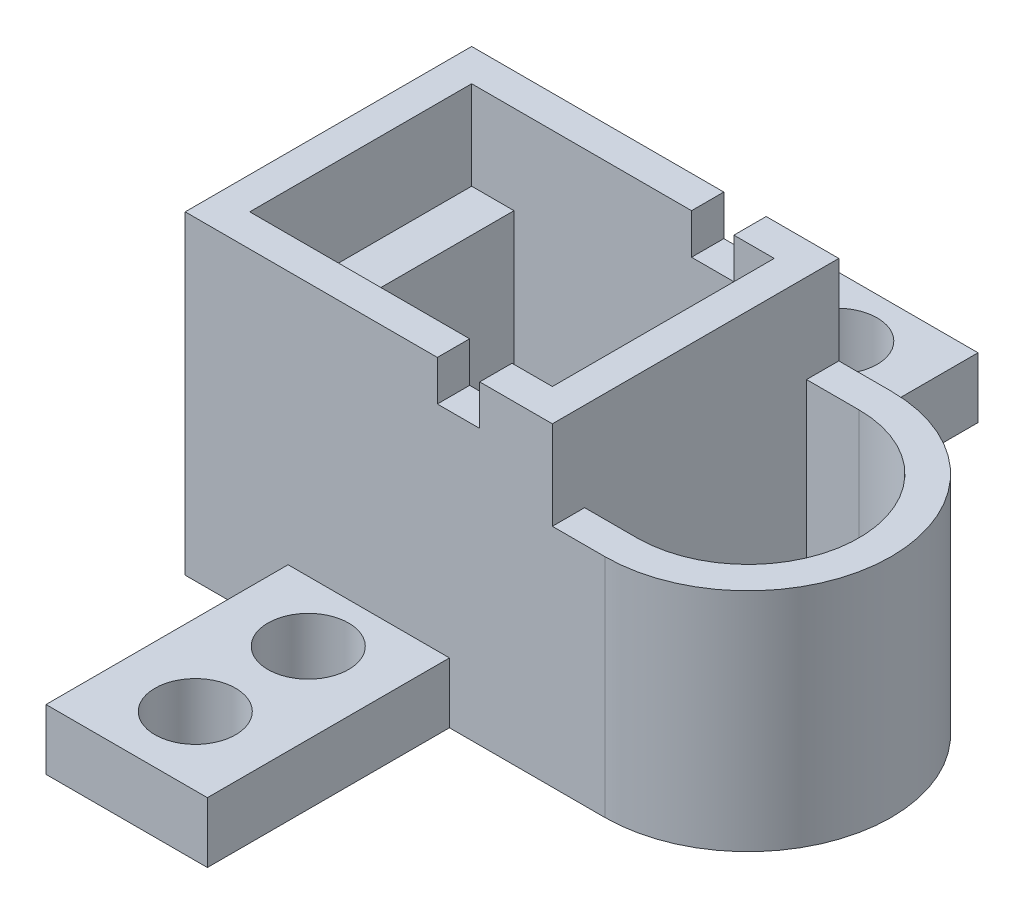
SolidWorks part; units mm, degrees
ref_plane "Спереди" through (0, 0, 0) normal (0, 0, 1) x (1, 0, 0)
ref_plane "Сверху" through (0, 0, 0) normal (0, 1, 0) x (1, 0, 0)
ref_plane "Справа" through (0, 0, 0) normal (1, 0, 0) x (0, 0, -1)
sketch "Эскиз1" plane through (0, 0, 0) normal (0, 1, 0) x (1, 0, 0)
  line L0 (4.55, 2.75) -> (5.85, 2.75)
  line L1 (-3.75, -2.75) -> (3.75, -2.75)
  line L2 (-3.75, -2.75) -> (-3.75, 2.75)
  line L3 (-3.75, 2.75) -> (3.75, 2.75)
  line L4 (3.75, -2.75) -> (3.75, 2.75)
  line L5 (-3.75, -2.75) -> (3.75, 2.75) construction
  line L6 (-3.75, 2.75) -> (3.75, -2.75) construction
  line L7 (-4.55, -3.55) -> (4.55, -3.55)
  line L8 (-4.55, -3.55) -> (-4.55, 3.55)
  line L9 (-4.55, 3.55) -> (4.55, 3.55)
  line L10 (4.55, -3.55) -> (4.55, 3.55)
  line L11 (-4.55, -3.55) -> (4.55, 3.55) construction
  line L12 (-4.55, 3.55) -> (4.55, -3.55) construction
  line L13 (-2.7, -2.75) -> (2.7, -2.75)
  line L14 (-2.7, -2.75) -> (-2.7, 2.75)
  line L15 (-2.7, 2.75) -> (2.7, 2.75)
  line L16 (2.7, -2.75) -> (2.7, 2.75)
  line L17 (-2.7, -2.75) -> (2.7, 2.75) construction
  line L18 (-2.7, 2.75) -> (2.7, -2.75) construction
  line L19 (4.55, -2.75) -> (5.85, -2.75)
  line L20 (4.55, 3.55) -> (5.85, 3.55)
  line L21 (4.55, -3.55) -> (5.85, -3.55)
  line L22 (5.85, 2.75) -> (5.85, -2.75) construction
  arc A0 (5.85, -2.75) -> (5.85, 2.75) centre (5.85, 0) ccw
  arc A1 (5.85, 3.55) -> (5.85, -3.55) centre (5.85, 0) cw
  point P0 (0, 0)
  point P6 (0, 0)
  point P10 (6.3693, 3.55)
  point P11 (0, 0)
  point P17 (0, 0)
  point P25 (0, 0)
  point P26 (7.3906, 3.55)
  dimension "D6" = 1.3
  dimension "D7" = 3.55
  dimension "D10" = 2.75
  dimension "D1" = 5.5
  dimension "D2" = 7.5
  dimension "D3" = 0.8
  dimension "D4" = 0.8
  dimension "D5" = 5.4
  dimension "D8" = 0.8
  dimension "D9" = 0.8
extrude "Бобышка-Вытянуть1" add sketch "Эскиз1" along normal blind 7.2 contours L7 L10 L9 L8 L4 L1 L2 L3 region at (4.4346, 0, 0)
extrude "Бобышка-Вытянуть2" add sketch "Эскиз1<3>" along normal blind 5 contours L1 L14 L3 L2 | L16 L1 L4 L3 region at (-3.225, 0, 0) region at (3.225, 0, 0)
sketch "Эскиз1<3>" plane through (0, 0, 0) normal (0, 1, 0) x (1, 0, 0) same geometry as "Эскиз1"
extrude "Бобышка-Вытянуть3" add sketch "Эскиз1<4>" against normal blind 0.6 contours L8 L9 L10 L7
sketch "Эскиз1<4>" plane through (0, 0, 0) normal (0, 1, 0) x (1, 0, 0) same geometry as "Эскиз1"
extrude "Бобышка-Вытянуть4" add sketch "Эскиз1<5>" along normal blind 5 contours A1 L20 L10 L0 A0 L19 L21 region at (4.636, 0, -3.15)
sketch "Эскиз1<5>" plane through (0, 0, 0) normal (0, 1, 0) x (1, 0, 0) same geometry as "Эскиз1"
extrude "Бобышка-Вытянуть5" add sketch "Эскиз1<6>" against normal blind 0.6 contours L19 A0 L0 L10 | A1 L20 L10 L0 A0 L19 L21 region at (4.636, 0, -3.15) region at (6.3344, 0, 0)
sketch "Эскиз1<6>" plane through (0, 0, 0) normal (0, 1, 0) x (1, 0, 0) same geometry as "Эскиз1"
sketch "Эскиз2" plane through (0, 0, -3.55) normal (0, 0, -1) x (-1, 0, 0)
  line L0 (4.55, 7.2) -> (-4.55, 7.2) construction
  line L1 (-1.7, 6.2) -> (-2.75, 6.2)
  line L2 (-1.7, 6.2) -> (-1.7, 7.2)
  line L3 (-1.7, 7.2) -> (-2.75, 7.2)
  line L4 (-2.75, 6.2) -> (-2.75, 7.2)
  line L5 (-1.7, 6.2) -> (-2.75, 7.2) construction
  line L6 (-1.7, 7.2) -> (-2.75, 6.2) construction
  line L7 (-4.55, 7.2) -> (-4.55, 5) construction
  point P0 (-2.225, 6.7)
  dimension "D1" = 1.05
  dimension "D2" = 1
  dimension "D3" = 1.8
extrude "Вырез-Вытянуть1" cut sketch "Эскиз2" against normal blind 7.1
sketch "Эскиз4" plane through (0, 0, 3.55) normal (0, 0, 1) x (1, 0, 0)
  line L0 (-2, -0.6) -> (2, -0.6)
  line L1 (-2, -0.6) -> (-2, 0.9)
  line L2 (2, -0.6) -> (2, 0.9)
  line L3 (-2, 0.9) -> (2, 0.9)
  line L4 (-4.55, -0.6) -> (5.85, -0.6) construction
  dimension "D1" = 4
  dimension "D2" = 1.5
extrude "Бобышка-Вытянуть7" add sketch "Эскиз4" along normal blind 6
sketch "Эскиз5" plane through (0, 0.9, 0) normal (0, 1, 0) x (1, 0, 0)
  line L0 (-4.55, -3.55) -> (1.7, -3.55) construction
  circle A0 centre (0, -5.05) radius 1
  circle A1 centre (0, -7.85) radius 1
  dimension "D1" = 2
  dimension "D3" = 1.5
  dimension "D2" = 2
extrude "Вырез-Вытянуть2" cut sketch "Эскиз5" against normal blind 1.5
pattern_linear "Линейный массив2" count 2 spacing 13.1 along (0, 0, -1) of "Бобышка-Вытянуть7", "Вырез-Вытянуть2"
